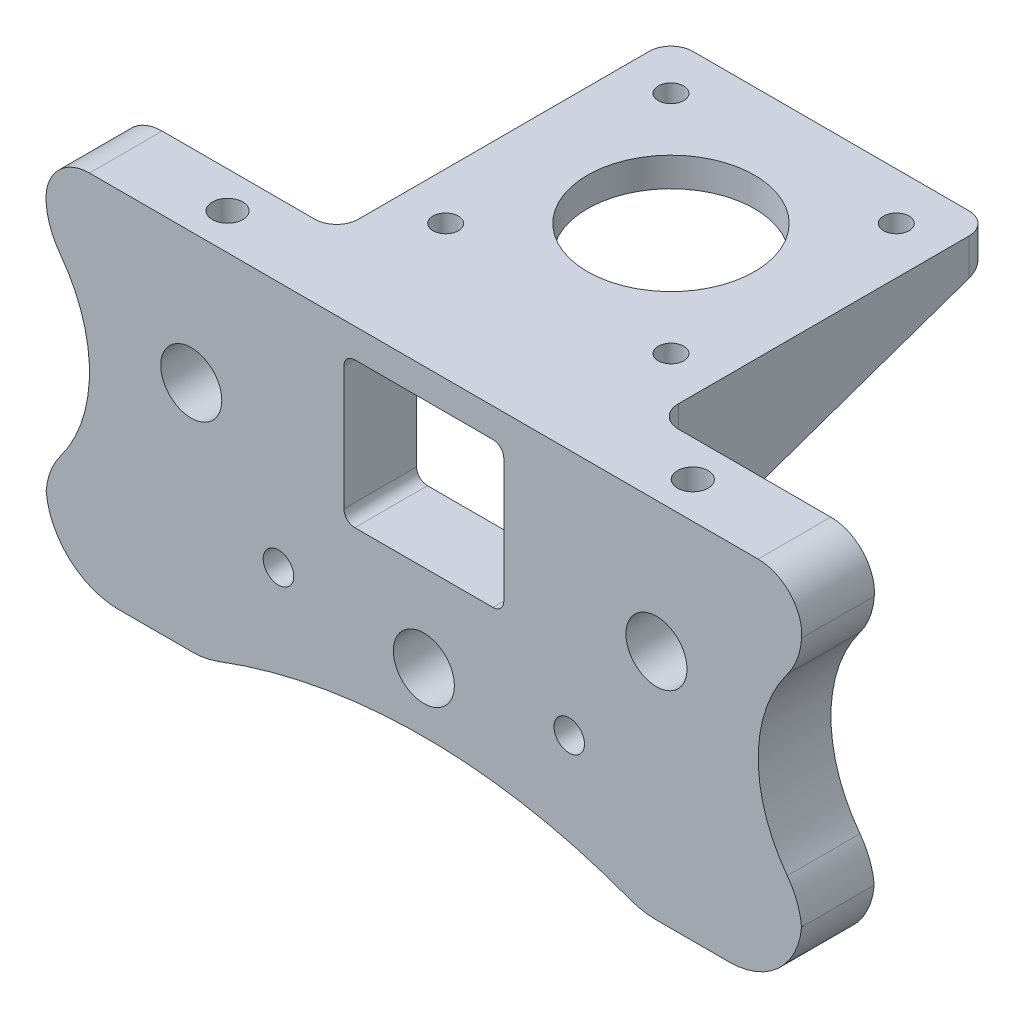
SolidWorks part; units mm, degrees
ref_plane "Front Plane" through (0, 0, 0) normal (0, 0, 1) x (1, 0, 0)
ref_plane "Top Plane" through (0, 0, 0) normal (0, 1, 0) x (1, 0, 0)
ref_plane "Right Plane" through (0, 0, 0) normal (1, 0, 0) x (0, 0, -1)
sketch "Sketch1" plane through (0, 0, 0) normal (0, 0, 1) x (1, 0, 0)
  line L0 (-52, 25) -> (52, -25) construction
  line L1 (-52, 25) -> (52, 25)
  line L2 (-52, 25) -> (-52, 15.5657)
  line L3 (-52, -25) -> (-30, -25)
  line L4 (52, 25) -> (52, 15.5657)
  line L5 (0, 0) -> (0, 48.9699) construction
  line L6 (-52, -13) -> (-52, -25)
  line L7 (52, -13) -> (52, -25)
  line L8 (30, -25) -> (52, -25)
  line L9 (-9.5, 21) -> (9.5, 21)
  line L10 (11, 19.5) -> (11, 2.5)
  line L11 (9.5, 1) -> (-9.5, 1)
  line L12 (-11, 2.5) -> (-11, 19.5)
  arc A0 (-52, 15.5657) -> (-52, -13) centre (-66, 1.2829) cw
  arc A1 (52, 15.5657) -> (52, -13) centre (66, 1.2829) ccw
  arc A2 (-30, -25) -> (30, -25) centre (0, -99.162) cw
  circle A3 centre (0, -11) radius 4.2
  circle A4 centre (-32, 7) radius 4.2
  circle A5 centre (32, 7) radius 4.2
  arc A6 (-9.5, 1) -> (-11, 2.5) centre (-9.5, 2.5) cw
  arc A7 (11, 2.5) -> (9.5, 1) centre (9.5, 2.5) cw
  arc A8 (9.5, 21) -> (11, 19.5) centre (9.5, 19.5) cw
  arc A9 (-9.5, 21) -> (-11, 19.5) centre (-9.5, 19.5) ccw
  point P4 (0, 0)
  dimension "D3" = 20
  dimension "D7" = 18
  dimension "D8" = 8.4
  dimension "D14" = 1.5
  dimension "D17" = 80
  dimension "D1" = 50
  dimension "D2" = 104
  dimension "D4" = 14
  dimension "D5" = 14
  dimension "D6" = 60
  dimension "D9" = 64
  dimension "D10" = 18
  dimension "D11" = 22
  dimension "D12" = 20
  dimension "D13" = 4
  dimension "D15" = 12
extrude "Boss-Extrude1" add sketch "Sketch1" along normal mid plane 10
fillet "Fillet1" radius 10 8 edges at (52, 15.5657, 0) (52, -13, 0) (52, -25, 0) (30, -25, 0) (-30, -25, 0) (-52, -25, 0) (-52, -13, 0) (-52, 15.5657, 0)
fillet "Fillet2" radius 6 2 edges at (52, 25, 0) (-52, 25, 0)
sketch "Sketch2" plane through (0, 25, -30) normal (0, 1, 0) x (-1, 0, 0)
  line L0 (-45.99, 25) -> (45.99, 25) construction
  line L1 (-21, 25) -> (21, 25)
  line L2 (-21, 25) -> (-21, -21)
  line L3 (-21, -21) -> (21, -21)
  line L4 (21, 25) -> (21, -21)
  line L5 (0, 30) -> (0, 51.7954) construction
  line L6 (0, 1) -> (0, 20.5767) construction
  line L7 (0, 1) -> (-18.4581, 1) construction
  circle A1 centre (0, 1) radius 11.5
  circle A2 centre (15.5, 16.5) radius 1.75
  circle A3 centre (-15.5, 16.5) radius 1.75
  circle A4 centre (-15.5, -14.5) radius 1.75
  circle A5 centre (15.5, -14.5) radius 1.75
  dimension "D3" = 22
  dimension "D4" = 23
  dimension "D5" = 31
  dimension "D7" = 3.5
  dimension "D1" = 46
  dimension "D2" = 42
  dimension "D6" = 31
  dimension "D8" = 6.5
extrude "Boss-Extrude2" add sketch "Sketch2" against normal blind 4
sketch "Sketch3" plane through (0, 21, 0) normal (0, -1, 0) x (1, 0, 0)
  circle A0 centre (-15.5, -44.5) radius 3
  circle A1 centre (15.5, -44.5) radius 3
  circle A2 centre (15.5, -13.5) radius 3
  circle A3 centre (-15.5, -13.5) radius 3
  dimension "D1" = 6
extrude "Cut-Extrude1" cut sketch "Sketch3" along normal up to next from offset 1 offset against normal yes
sketch "Sketch4" plane through (0, 25, 0) normal (0, 1, 0) x (1, 0, 0)
  line L0 (0, 0) -> (0, 64.113) construction
  circle A0 centre (-32, 0) radius 1.75
  circle A1 centre (32, 0) radius 1.75
  dimension "D1" = 64
  dimension "D2" = 3.5
extrude "Cut-Extrude2" cut sketch "Sketch4" against normal up to next
sketch "Sketch5" plane through (0, 25, 0) normal (0, 1, 0) x (1, 0, 0)
  circle A0 centre (-32, 0) radius 2.1
  circle A1 centre (32, 0) radius 2.1
  dimension "D1" = 4.2
extrude "Cut-Extrude3" cut sketch "Sketch5" against normal blind 4
sketch "Sketch6" plane through (21, 0, 0) normal (1, 0, 0) x (0, 0, -1)
  line L0 (51, 25) -> (5, 25)
  line L1 (5, 25) -> (5, 5)
  line L2 (5, -10.7171) -> (5, 13.2829) construction
  line L3 (5, 5) -> (51, 21)
  line L4 (51, 21) -> (51, 25)
  dimension "D1" = 20
  dimension "D2" = 4
extrude "Boss-Extrude3" add sketch "Sketch6" against normal blind 2 and the other way blind 1
mirror "Mirror1" about plane through (0, 0, 0) normal (1, 0, 0) of "Boss-Extrude3"
fillet "Fillet3" radius 2 2 edges at (-14.25, 21, -5) (14.25, 21, -5)
fillet "Fillet4" radius 3 4 edges at (22, 15, -5) (-22, 15, -5) (-22, 23, -51) (22, 23, -51)
sketch "Sketch7" plane through (0, 0, 5) normal (0, 0, 1) x (1, 0, 0)
  line L0 (0, 0) -> (0, -38.8974) construction
  line L1 (31.8867, -25) -> (42, -25) construction
  circle A0 centre (-20, -9) radius 1.75
  circle A1 centre (20, -9) radius 1.75
  dimension "D1" = 40
  dimension "D2" = 3.5
  dimension "D3" = 16
extrude "Cut-Extrude4" cut sketch "Sketch7" against normal through all
sketch "Sketch8" plane through (0, 0, 5) normal (0, 0, 1) x (1, 0, 0)
  circle A0 centre (-20, -9) radius 2.1
  circle A1 centre (20, -9) radius 2.1
  dimension "D1" = 4.2
extrude "Cut-Extrude5" cut sketch "Sketch8" against normal blind 4
chamfer "Chamfer1" distance 0.5 angle 45 4 edges at (-32, 21, 1.75) (32, 21, 1.75) (-18.25, -9, 1) (21.75, -9, 1)
